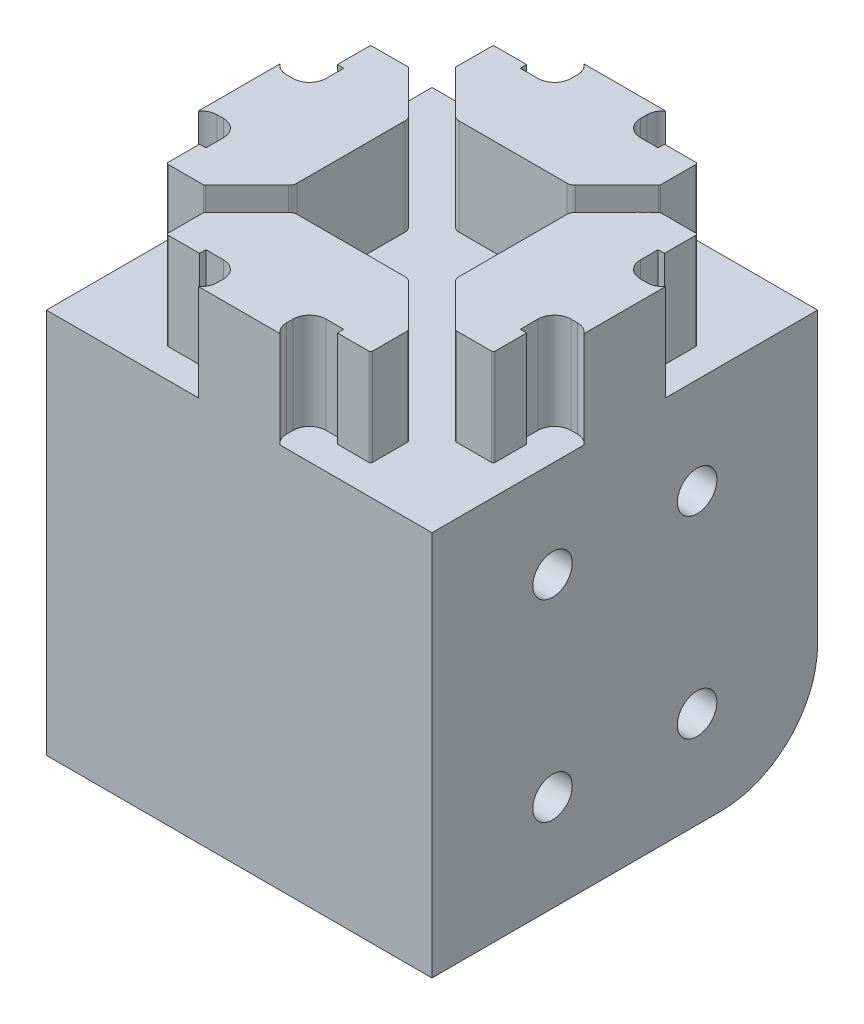
SolidWorks part; units mm, degrees
ref_plane "Front Plane" through (0, 0, 0) normal (0, 0, 1) x (1, 0, 0)
ref_plane "Top Plane" through (0, 0, 0) normal (0, 1, 0) x (1, 0, 0)
ref_plane "Right Plane" through (0, 0, 0) normal (1, 0, 0) x (0, 0, -1)
sketch "Sketch1" plane through (0, 0, 0) normal (0, 1, 0) x (1, 0, 0)
  line L1 (-20, -20) -> (20, -20)
  line L2 (-20, -20) -> (-20, 20)
  line L3 (-20, 20) -> (20, 20)
  line L4 (20, -20) -> (20, 20)
  line L5 (-20, -20) -> (20, 20) construction
  line L6 (-20, 20) -> (20, -20) construction
  point P0 (0, 0)
  dimension "D1" = 40
  dimension "D2" = 40
extrude "Boss-Extrude1" add sketch "Sketch1" along normal mid plane 40 contours L3 L4 L1 L2
sketch "Sketch2" plane through (0, 0, 0) normal (1, 0, 0) x (0, 0, -1)
  point P0 (0, 0)
  line B0 (-7.5, -10) -> (-7.5, 10) construction
  line B1 (7.5, -10) -> (7.5, 10) construction
  circle B2 centre (-7.5, 10) radius 2.05
  circle B3 centre (7.5, 10) radius 2.05
  circle B4 centre (-7.5, -10) radius 2.05
  circle B5 centre (7.5, -10) radius 2.05
sketch_block_instance "Block1-1"
sketch_block "Block1" parameters "D1"=4.1, "D2"=20, "D3"=15
extrude "Cut-Extrude1" cut sketch "Sketch2" against normal through all from offset 13
mirror "Mirror1" about plane through (0, 0, 0) normal (1, 0, 0) of "Cut-Extrude1"
sketch "Sketch3" plane through (0, 20, 0) normal (0, 1, 0) x (1, 0, 0)
  line L0 (11.8267, 9.3942) -> (11.8267, 9.4899)
  line L1 (11.8267, 9.4899) -> (11.9223, 9.4899)
  line L2 (11.9223, 9.4899) -> (12.39, 9.9576)
  line L3 (12.39, 9.9576) -> (12.39, 10.0532)
  line L4 (12.39, 10.0532) -> (12.4857, 10.0532)
  line L5 (12.4857, 10.0532) -> (12.9739, 10.5414)
  line L6 (13.1153, 10.6) -> (16.76, 10.6)
  line L7 (16.96, 10.4) -> (16.96, 7.15)
  line L8 (16.96, 7.15) -> (16.3, 7.15)
  line L9 (16.3, 7.15) -> (16.3, 5.32)
  line L10 (18.02, 3.6) -> (18.68, 3.6)
  line L11 (20.4, 5.32) -> (20.4, 17)
  line L12 (17, 20.4) -> (5.32, 20.4)
  line L13 (3.6, 18.68) -> (3.6, 18.02)
  line L14 (5.32, 16.3) -> (7.15, 16.3)
  line L15 (7.15, 16.3) -> (7.15, 16.96)
  line L16 (7.15, 16.96) -> (10.4, 16.96)
  line L17 (10.6, 16.76) -> (10.6, 13.1153)
  line L18 (10.5414, 12.9739) -> (6.237, 8.6695)
  line L19 (5.5865, 8.4) -> (-5.5865, 8.4)
  line L20 (-6.237, 8.6695) -> (-10.5414, 12.9739)
  line L21 (-10.6, 13.1153) -> (-10.6, 16.76)
  line L22 (-10.4, 16.96) -> (-7.15, 16.96)
  line L23 (-7.15, 16.96) -> (-7.15, 16.3)
  line L24 (-7.15, 16.3) -> (-5.32, 16.3)
  line L25 (-3.6, 18.02) -> (-3.6, 18.68)
  line L26 (-5.32, 20.4) -> (-17, 20.4)
  line L27 (-20.4, 17) -> (-20.4, 5.32)
  line L28 (-18.68, 3.6) -> (-18.02, 3.6)
  line L29 (-16.3, 5.32) -> (-16.3, 7.15)
  line L30 (-16.3, 7.15) -> (-16.96, 7.15)
  line L31 (-16.96, 7.15) -> (-16.96, 10.4)
  line L32 (-16.76, 10.6) -> (-13.1153, 10.6)
  line L33 (-12.9739, 10.5414) -> (-8.6695, 6.237)
  line L34 (-8.4, 5.5865) -> (-8.4, -5.5865)
  line L35 (-8.6695, -6.237) -> (-12.9739, -10.5414)
  line L36 (-13.1153, -10.6) -> (-16.76, -10.6)
  line L37 (-16.96, -10.4) -> (-16.96, -7.15)
  line L38 (-16.96, -7.15) -> (-16.3, -7.15)
  line L39 (-16.3, -7.15) -> (-16.3, -5.32)
  line L40 (-18.02, -3.6) -> (-18.68, -3.6)
  line L41 (-20.4, -5.32) -> (-20.4, -17)
  line L42 (-17, -20.4) -> (-5.32, -20.4)
  line L43 (-3.6, -18.68) -> (-3.6, -18.02)
  line L44 (-5.32, -16.3) -> (-7.15, -16.3)
  line L45 (-7.15, -16.3) -> (-7.15, -16.96)
  line L46 (-7.15, -16.96) -> (-10.4, -16.96)
  line L47 (-10.6, -16.76) -> (-10.6, -13.1153)
  line L48 (-10.5414, -12.9739) -> (-6.237, -8.6695)
  line L49 (-5.5865, -8.4) -> (5.5865, -8.4)
  line L50 (6.237, -8.6695) -> (10.5414, -12.9739)
  line L51 (10.6, -13.1153) -> (10.6, -16.76)
  line L52 (10.4, -16.96) -> (7.15, -16.96)
  line L53 (7.15, -16.96) -> (7.15, -16.3)
  line L54 (7.15, -16.3) -> (5.32, -16.3)
  line L55 (3.6, -18.02) -> (3.6, -18.68)
  line L56 (5.32, -20.4) -> (17, -20.4)
  line L57 (20.4, -17) -> (20.4, -5.32)
  line L58 (18.68, -3.6) -> (18.02, -3.6)
  line L59 (16.3, -5.32) -> (16.3, -7.15)
  line L60 (16.3, -7.15) -> (16.96, -7.15)
  line L61 (16.96, -7.15) -> (16.96, -10.4)
  line L62 (16.76, -10.6) -> (13.1153, -10.6)
  line L63 (12.9739, -10.5414) -> (8.6695, -6.237)
  line L64 (8.4, -5.5865) -> (8.4, 5.5865)
  line L65 (8.6695, 6.237) -> (11.8267, 9.3942)
  line L66 (11.4267, 9.5599) -> (11.4267, 9.8899)
  line L67 (11.4267, 9.8899) -> (11.7567, 9.8899)
  line L68 (11.7567, 9.8899) -> (11.99, 10.1232)
  line L69 (11.99, 10.1232) -> (11.99, 10.4532)
  line L70 (11.99, 10.4532) -> (12.32, 10.4532)
  line L71 (12.32, 10.4532) -> (12.691, 10.8243)
  line L72 (13.1153, 11) -> (16.76, 11)
  line L73 (17.36, 10.4) -> (17.36, 6.75)
  line L74 (17.36, 6.75) -> (16.7, 6.75)
  line L75 (16.7, 6.75) -> (16.7, 5.32)
  line L76 (18.02, 4) -> (18.68, 4)
  line L77 (20, 5.32) -> (20, 17)
  line L78 (17, 20) -> (5.32, 20)
  line L79 (4, 18.68) -> (4, 18.02)
  line L80 (5.32, 16.7) -> (6.75, 16.7)
  line L81 (6.75, 16.7) -> (6.75, 17.36)
  line L82 (6.75, 17.36) -> (10.4, 17.36)
  line L83 (11, 16.76) -> (11, 13.1153)
  line L84 (10.8243, 12.691) -> (6.5199, 8.3866)
  line L85 (5.5865, 8) -> (-5.5865, 8)
  line L86 (-6.5199, 8.3866) -> (-10.8243, 12.691)
  line L87 (-11, 13.1153) -> (-11, 16.76)
  line L88 (-10.4, 17.36) -> (-6.75, 17.36)
  line L89 (-6.75, 17.36) -> (-6.75, 16.7)
  line L90 (-6.75, 16.7) -> (-5.32, 16.7)
  line L91 (-4, 18.02) -> (-4, 18.68)
  line L92 (-5.32, 20) -> (-17, 20)
  line L93 (-20, 17) -> (-20, 5.32)
  line L94 (-18.68, 4) -> (-18.02, 4)
  line L95 (-16.7, 5.32) -> (-16.7, 6.75)
  line L96 (-16.7, 6.75) -> (-17.36, 6.75)
  line L97 (-17.36, 6.75) -> (-17.36, 10.4)
  line L98 (-16.76, 11) -> (-13.1153, 11)
  line L99 (-12.691, 10.8243) -> (-8.3866, 6.5199)
  line L100 (-8, 5.5865) -> (-8, -5.5865)
  line L101 (-8.3866, -6.5199) -> (-12.691, -10.8243)
  line L102 (-13.1153, -11) -> (-16.76, -11)
  line L103 (-17.36, -10.4) -> (-17.36, -6.75)
  line L104 (-17.36, -6.75) -> (-16.7, -6.75)
  line L105 (-16.7, -6.75) -> (-16.7, -5.32)
  line L106 (-18.02, -4) -> (-18.68, -4)
  line L107 (-20, -5.32) -> (-20, -17)
  line L108 (-17, -20) -> (-5.32, -20)
  line L109 (-4, -18.68) -> (-4, -18.02)
  line L110 (-5.32, -16.7) -> (-6.75, -16.7)
  line L111 (-6.75, -16.7) -> (-6.75, -17.36)
  line L112 (-6.75, -17.36) -> (-10.4, -17.36)
  line L113 (-11, -16.76) -> (-11, -13.1153)
  line L114 (-10.8243, -12.691) -> (-6.5199, -8.3866)
  line L115 (-5.5865, -8) -> (5.5865, -8)
  line L116 (6.5199, -8.3866) -> (10.8243, -12.691)
  line L117 (11, -13.1153) -> (11, -16.76)
  line L118 (10.4, -17.36) -> (6.75, -17.36)
  line L119 (6.75, -17.36) -> (6.75, -16.7)
  line L120 (6.75, -16.7) -> (5.32, -16.7)
  line L121 (4, -18.02) -> (4, -18.68)
  line L122 (5.32, -20) -> (17, -20)
  line L123 (20, -17) -> (20, -5.32)
  line L124 (18.68, -4) -> (18.02, -4)
  line L125 (16.7, -5.32) -> (16.7, -6.75)
  line L126 (16.7, -6.75) -> (17.36, -6.75)
  line L127 (17.36, -6.75) -> (17.36, -10.4)
  line L128 (16.76, -11) -> (13.1153, -11)
  line L129 (12.691, -10.8243) -> (8.3866, -6.5199)
  line L130 (8, -5.5865) -> (8, 5.5865)
  line L131 (8.3866, 6.5199) -> (11.4267, 9.5599)
  line L132 (11.4267, 9.5599) -> (11.4267, 9.8899)
  line L133 (11.4267, 9.8899) -> (11.7567, 9.8899)
  line L134 (11.7567, 9.8899) -> (11.99, 10.1232)
  line L135 (11.99, 10.1232) -> (11.99, 10.4532)
  line L136 (11.99, 10.4532) -> (12.32, 10.4532)
  line L137 (12.32, 10.4532) -> (12.691, 10.8243)
  line L138 (13.1153, 11) -> (16.76, 11)
  line L139 (17.36, 10.4) -> (17.36, 6.75)
  line L140 (17.36, 6.75) -> (16.7, 6.75)
  line L141 (16.7, 6.75) -> (16.7, 5.32)
  line L142 (18.02, 4) -> (18.68, 4)
  line L143 (20, 5.32) -> (20, 17)
  line L144 (17, 20) -> (5.32, 20)
  line L145 (4, 18.68) -> (4, 18.02)
  line L146 (5.32, 16.7) -> (6.75, 16.7)
  line L147 (6.75, 16.7) -> (6.75, 17.36)
  line L148 (6.75, 17.36) -> (10.4, 17.36)
  line L149 (11, 16.76) -> (11, 13.1153)
  line L150 (10.8243, 12.691) -> (6.5199, 8.3866)
  line L151 (5.5865, 8) -> (-5.5865, 8)
  line L152 (-6.5199, 8.3866) -> (-10.8243, 12.691)
  line L153 (-11, 13.1153) -> (-11, 16.76)
  line L154 (-10.4, 17.36) -> (-6.75, 17.36)
  line L155 (-6.75, 17.36) -> (-6.75, 16.7)
  line L156 (-6.75, 16.7) -> (-5.32, 16.7)
  line L157 (-4, 18.02) -> (-4, 18.68)
  line L158 (-5.32, 20) -> (-17, 20)
  line L159 (-20, 17) -> (-20, 5.32)
  line L160 (-18.68, 4) -> (-18.02, 4)
  line L161 (-16.7, 5.32) -> (-16.7, 6.75)
  line L162 (-16.7, 6.75) -> (-17.36, 6.75)
  line L163 (-17.36, 6.75) -> (-17.36, 10.4)
  line L164 (-16.76, 11) -> (-13.1153, 11)
  line L165 (-12.691, 10.8243) -> (-8.3866, 6.5199)
  line L166 (-8, 5.5865) -> (-8, -5.5865)
  line L167 (-8.3866, -6.5199) -> (-12.691, -10.8243)
  line L168 (-13.1153, -11) -> (-16.76, -11)
  line L169 (-17.36, -10.4) -> (-17.36, -6.75)
  line L170 (-17.36, -6.75) -> (-16.7, -6.75)
  line L171 (-16.7, -6.75) -> (-16.7, -5.32)
  line L172 (-18.02, -4) -> (-18.68, -4)
  line L173 (-20, -5.32) -> (-20, -17)
  line L174 (-17, -20) -> (-5.32, -20)
  line L175 (-4, -18.68) -> (-4, -18.02)
  line L176 (-5.32, -16.7) -> (-6.75, -16.7)
  line L177 (-6.75, -16.7) -> (-6.75, -17.36)
  line L178 (-6.75, -17.36) -> (-10.4, -17.36)
  line L179 (-11, -16.76) -> (-11, -13.1153)
  line L180 (-10.8243, -12.691) -> (-6.5199, -8.3866)
  line L181 (-5.5865, -8) -> (5.5865, -8)
  line L182 (6.5199, -8.3866) -> (10.8243, -12.691)
  line L183 (11, -13.1153) -> (11, -16.76)
  line L184 (10.4, -17.36) -> (6.75, -17.36)
  line L185 (6.75, -17.36) -> (6.75, -16.7)
  line L186 (6.75, -16.7) -> (5.32, -16.7)
  line L187 (4, -18.02) -> (4, -18.68)
  line L188 (5.32, -20) -> (17, -20)
  line L189 (20, -17) -> (20, -5.32)
  line L190 (18.68, -4) -> (18.02, -4)
  line L191 (16.7, -5.32) -> (16.7, -6.75)
  line L192 (16.7, -6.75) -> (17.36, -6.75)
  line L193 (17.36, -6.75) -> (17.36, -10.4)
  line L194 (16.76, -11) -> (13.1153, -11)
  line L195 (12.691, -10.8243) -> (8.3866, -6.5199)
  line L196 (8, -5.5865) -> (8, 5.5865)
  line L197 (8.3866, 6.5199) -> (11.4267, 9.5599)
  line L202 (-20, 20) -> (-20, -20)
  line L203 (-20, -20) -> (20, -20)
  line L204 (20, -20) -> (20, 20)
  line L205 (20, 20) -> (-20, 20)
  line L206 (-20, 20) -> (-20, -20)
  line L207 (-20, -20) -> (20, -20)
  line L208 (20, -20) -> (20, 20)
  line L209 (20, 20) -> (-20, 20)
  arc A0 (13.1153, 10.6) -> (12.9739, 10.5414) centre (13.1153, 10.4) ccw
  arc A1 (16.96, 10.4) -> (16.76, 10.6) centre (16.76, 10.4) ccw
  arc A2 (16.3, 5.32) -> (18.02, 3.6) centre (18.02, 5.32) ccw
  arc A3 (18.68, 3.6) -> (20.4, 5.32) centre (18.68, 5.32) ccw
  arc A4 (20.4, 17) -> (17, 20.4) centre (17, 17) ccw
  arc A5 (5.32, 20.4) -> (3.6, 18.68) centre (5.32, 18.68) ccw
  arc A6 (3.6, 18.02) -> (5.32, 16.3) centre (5.32, 18.02) ccw
  arc A7 (10.6, 16.76) -> (10.4, 16.96) centre (10.4, 16.76) ccw
  arc A8 (10.5414, 12.9739) -> (10.6, 13.1153) centre (10.4, 13.1153) ccw
  arc A9 (5.5865, 8.4) -> (6.237, 8.6695) centre (5.5865, 9.32) ccw
  arc A10 (-6.237, 8.6695) -> (-5.5865, 8.4) centre (-5.5865, 9.32) ccw
  arc A11 (-10.6, 13.1153) -> (-10.5414, 12.9739) centre (-10.4, 13.1153) ccw
  arc A12 (-10.4, 16.96) -> (-10.6, 16.76) centre (-10.4, 16.76) ccw
  arc A13 (-5.32, 16.3) -> (-3.6, 18.02) centre (-5.32, 18.02) ccw
  arc A14 (-3.6, 18.68) -> (-5.32, 20.4) centre (-5.32, 18.68) ccw
  arc A15 (-17, 20.4) -> (-20.4, 17) centre (-17, 17) ccw
  arc A16 (-20.4, 5.32) -> (-18.68, 3.6) centre (-18.68, 5.32) ccw
  arc A17 (-18.02, 3.6) -> (-16.3, 5.32) centre (-18.02, 5.32) ccw
  arc A18 (-16.76, 10.6) -> (-16.96, 10.4) centre (-16.76, 10.4) ccw
  arc A19 (-12.9739, 10.5414) -> (-13.1153, 10.6) centre (-13.1153, 10.4) ccw
  arc A20 (-8.4, 5.5865) -> (-8.6695, 6.237) centre (-9.32, 5.5865) ccw
  arc A21 (-8.6695, -6.237) -> (-8.4, -5.5865) centre (-9.32, -5.5865) ccw
  arc A22 (-13.1153, -10.6) -> (-12.9739, -10.5414) centre (-13.1153, -10.4) ccw
  arc A23 (-16.96, -10.4) -> (-16.76, -10.6) centre (-16.76, -10.4) ccw
  arc A24 (-16.3, -5.32) -> (-18.02, -3.6) centre (-18.02, -5.32) ccw
  arc A25 (-18.68, -3.6) -> (-20.4, -5.32) centre (-18.68, -5.32) ccw
  arc A26 (-20.4, -17) -> (-17, -20.4) centre (-17, -17) ccw
  arc A27 (-5.32, -20.4) -> (-3.6, -18.68) centre (-5.32, -18.68) ccw
  arc A28 (-3.6, -18.02) -> (-5.32, -16.3) centre (-5.32, -18.02) ccw
  arc A29 (-10.6, -16.76) -> (-10.4, -16.96) centre (-10.4, -16.76) ccw
  arc A30 (-10.5414, -12.9739) -> (-10.6, -13.1153) centre (-10.4, -13.1153) ccw
  arc A31 (-5.5865, -8.4) -> (-6.237, -8.6695) centre (-5.5865, -9.32) ccw
  arc A32 (6.237, -8.6695) -> (5.5865, -8.4) centre (5.5865, -9.32) ccw
  arc A33 (10.6, -13.1153) -> (10.5414, -12.9739) centre (10.4, -13.1153) ccw
  arc A34 (10.4, -16.96) -> (10.6, -16.76) centre (10.4, -16.76) ccw
  arc A35 (5.32, -16.3) -> (3.6, -18.02) centre (5.32, -18.02) ccw
  arc A36 (3.6, -18.68) -> (5.32, -20.4) centre (5.32, -18.68) ccw
  arc A37 (17, -20.4) -> (20.4, -17) centre (17, -17) ccw
  arc A38 (20.4, -5.32) -> (18.68, -3.6) centre (18.68, -5.32) ccw
  arc A39 (18.02, -3.6) -> (16.3, -5.32) centre (18.02, -5.32) ccw
  arc A40 (16.76, -10.6) -> (16.96, -10.4) centre (16.76, -10.4) ccw
  arc A41 (12.9739, -10.5414) -> (13.1153, -10.6) centre (13.1153, -10.4) ccw
  arc A42 (8.4, -5.5865) -> (8.6695, -6.237) centre (9.32, -5.5865) ccw
  arc A43 (8.6695, 6.237) -> (8.4, 5.5865) centre (9.32, 5.5865) ccw
  arc A44 (13.1153, 11) -> (12.691, 10.8243) centre (13.1153, 10.4) ccw
  arc A45 (17.36, 10.4) -> (16.76, 11) centre (16.76, 10.4) ccw
  arc A46 (16.7, 5.32) -> (18.02, 4) centre (18.02, 5.32) ccw
  arc A47 (18.68, 4) -> (20, 5.32) centre (18.68, 5.32) ccw
  arc A48 (20, 17) -> (17, 20) centre (17, 17) ccw
  arc A49 (5.32, 20) -> (4, 18.68) centre (5.32, 18.68) ccw
  arc A50 (4, 18.02) -> (5.32, 16.7) centre (5.32, 18.02) ccw
  arc A51 (11, 16.76) -> (10.4, 17.36) centre (10.4, 16.76) ccw
  arc A52 (10.8243, 12.691) -> (11, 13.1153) centre (10.4, 13.1153) ccw
  arc A53 (5.5865, 8) -> (6.5199, 8.3866) centre (5.5865, 9.32) ccw
  arc A54 (-6.5199, 8.3866) -> (-5.5865, 8) centre (-5.5865, 9.32) ccw
  arc A55 (-11, 13.1153) -> (-10.8243, 12.691) centre (-10.4, 13.1153) ccw
  arc A56 (-10.4, 17.36) -> (-11, 16.76) centre (-10.4, 16.76) ccw
  arc A57 (-5.32, 16.7) -> (-4, 18.02) centre (-5.32, 18.02) ccw
  arc A58 (-4, 18.68) -> (-5.32, 20) centre (-5.32, 18.68) ccw
  arc A59 (-17, 20) -> (-20, 17) centre (-17, 17) ccw
  arc A60 (-20, 5.32) -> (-18.68, 4) centre (-18.68, 5.32) ccw
  arc A61 (-18.02, 4) -> (-16.7, 5.32) centre (-18.02, 5.32) ccw
  arc A62 (-16.76, 11) -> (-17.36, 10.4) centre (-16.76, 10.4) ccw
  arc A63 (-12.691, 10.8243) -> (-13.1153, 11) centre (-13.1153, 10.4) ccw
  arc A64 (-8, 5.5865) -> (-8.3866, 6.5199) centre (-9.32, 5.5865) ccw
  arc A65 (-8.3866, -6.5199) -> (-8, -5.5865) centre (-9.32, -5.5865) ccw
  arc A66 (-13.1153, -11) -> (-12.691, -10.8243) centre (-13.1153, -10.4) ccw
  arc A67 (-17.36, -10.4) -> (-16.76, -11) centre (-16.76, -10.4) ccw
  arc A68 (-16.7, -5.32) -> (-18.02, -4) centre (-18.02, -5.32) ccw
  arc A69 (-18.68, -4) -> (-20, -5.32) centre (-18.68, -5.32) ccw
  arc A70 (-20, -17) -> (-17, -20) centre (-17, -17) ccw
  arc A71 (-5.32, -20) -> (-4, -18.68) centre (-5.32, -18.68) ccw
  arc A72 (-4, -18.02) -> (-5.32, -16.7) centre (-5.32, -18.02) ccw
  arc A73 (-11, -16.76) -> (-10.4, -17.36) centre (-10.4, -16.76) ccw
  arc A74 (-10.8243, -12.691) -> (-11, -13.1153) centre (-10.4, -13.1153) ccw
  arc A75 (-5.5865, -8) -> (-6.5199, -8.3866) centre (-5.5865, -9.32) ccw
  arc A76 (6.5199, -8.3866) -> (5.5865, -8) centre (5.5865, -9.32) ccw
  arc A77 (11, -13.1153) -> (10.8243, -12.691) centre (10.4, -13.1153) ccw
  arc A78 (10.4, -17.36) -> (11, -16.76) centre (10.4, -16.76) ccw
  arc A79 (5.32, -16.7) -> (4, -18.02) centre (5.32, -18.02) ccw
  arc A80 (4, -18.68) -> (5.32, -20) centre (5.32, -18.68) ccw
  arc A81 (17, -20) -> (20, -17) centre (17, -17) ccw
  arc A82 (20, -5.32) -> (18.68, -4) centre (18.68, -5.32) ccw
  arc A83 (18.02, -4) -> (16.7, -5.32) centre (18.02, -5.32) ccw
  arc A84 (16.76, -11) -> (17.36, -10.4) centre (16.76, -10.4) ccw
  arc A85 (12.691, -10.8243) -> (13.1153, -11) centre (13.1153, -10.4) ccw
  arc A86 (8, -5.5865) -> (8.3866, -6.5199) centre (9.32, -5.5865) ccw
  arc A87 (8.3866, 6.5199) -> (8, 5.5865) centre (9.32, 5.5865) ccw
  arc A88 (13.1153, 11) -> (12.691, 10.8243) centre (13.1153, 10.4) ccw
  arc A89 (17.36, 10.4) -> (16.76, 11) centre (16.76, 10.4) ccw
  arc A90 (16.7, 5.32) -> (18.02, 4) centre (18.02, 5.32) ccw
  arc A91 (18.68, 4) -> (20, 5.32) centre (18.68, 5.32) ccw
  arc A92 (20, 17) -> (17, 20) centre (17, 17) ccw
  arc A93 (5.32, 20) -> (4, 18.68) centre (5.32, 18.68) ccw
  arc A94 (4, 18.02) -> (5.32, 16.7) centre (5.32, 18.02) ccw
  arc A95 (11, 16.76) -> (10.4, 17.36) centre (10.4, 16.76) ccw
  arc A96 (10.8243, 12.691) -> (11, 13.1153) centre (10.4, 13.1153) ccw
  arc A97 (5.5865, 8) -> (6.5199, 8.3866) centre (5.5865, 9.32) ccw
  arc A98 (-6.5199, 8.3866) -> (-5.5865, 8) centre (-5.5865, 9.32) ccw
  arc A99 (-11, 13.1153) -> (-10.8243, 12.691) centre (-10.4, 13.1153) ccw
  arc A100 (-10.4, 17.36) -> (-11, 16.76) centre (-10.4, 16.76) ccw
  arc A101 (-5.32, 16.7) -> (-4, 18.02) centre (-5.32, 18.02) ccw
  arc A102 (-4, 18.68) -> (-5.32, 20) centre (-5.32, 18.68) ccw
  arc A103 (-17, 20) -> (-20, 17) centre (-17, 17) ccw
  arc A104 (-20, 5.32) -> (-18.68, 4) centre (-18.68, 5.32) ccw
  arc A105 (-18.02, 4) -> (-16.7, 5.32) centre (-18.02, 5.32) ccw
  arc A106 (-16.76, 11) -> (-17.36, 10.4) centre (-16.76, 10.4) ccw
  arc A107 (-12.691, 10.8243) -> (-13.1153, 11) centre (-13.1153, 10.4) ccw
  arc A108 (-8, 5.5865) -> (-8.3866, 6.5199) centre (-9.32, 5.5865) ccw
  arc A109 (-8.3866, -6.5199) -> (-8, -5.5865) centre (-9.32, -5.5865) ccw
  arc A110 (-13.1153, -11) -> (-12.691, -10.8243) centre (-13.1153, -10.4) ccw
  arc A111 (-17.36, -10.4) -> (-16.76, -11) centre (-16.76, -10.4) ccw
  arc A112 (-16.7, -5.32) -> (-18.02, -4) centre (-18.02, -5.32) ccw
  arc A113 (-18.68, -4) -> (-20, -5.32) centre (-18.68, -5.32) ccw
  arc A114 (-20, -17) -> (-17, -20) centre (-17, -17) ccw
  arc A115 (-5.32, -20) -> (-4, -18.68) centre (-5.32, -18.68) ccw
  arc A116 (-4, -18.02) -> (-5.32, -16.7) centre (-5.32, -18.02) ccw
  arc A117 (-11, -16.76) -> (-10.4, -17.36) centre (-10.4, -16.76) ccw
  arc A118 (-10.8243, -12.691) -> (-11, -13.1153) centre (-10.4, -13.1153) ccw
  arc A119 (-5.5865, -8) -> (-6.5199, -8.3866) centre (-5.5865, -9.32) ccw
  arc A120 (6.5199, -8.3866) -> (5.5865, -8) centre (5.5865, -9.32) ccw
  arc A121 (11, -13.1153) -> (10.8243, -12.691) centre (10.4, -13.1153) ccw
  arc A122 (10.4, -17.36) -> (11, -16.76) centre (10.4, -16.76) ccw
  arc A123 (5.32, -16.7) -> (4, -18.02) centre (5.32, -18.02) ccw
  arc A124 (4, -18.68) -> (5.32, -20) centre (5.32, -18.68) ccw
  arc A125 (17, -20) -> (20, -17) centre (17, -17) ccw
  arc A126 (20, -5.32) -> (18.68, -4) centre (18.68, -5.32) ccw
  arc A127 (18.02, -4) -> (16.7, -5.32) centre (18.02, -5.32) ccw
  arc A128 (16.76, -11) -> (17.36, -10.4) centre (16.76, -10.4) ccw
  arc A129 (12.691, -10.8243) -> (13.1153, -11) centre (13.1153, -10.4) ccw
  arc A130 (8, -5.5865) -> (8.3866, -6.5199) centre (9.32, -5.5865) ccw
  arc A131 (8.3866, 6.5199) -> (8, 5.5865) centre (9.32, 5.5865) ccw
  dimension "D1" = 0
  dimension "D2" = 0.4
  dimension "D3" = 0
extrude "Boss-Extrude2" add sketch "Sketch3" along normal blind 10 contours A25 L40 A24 L39 L38 L37 A23 L36 A22 L35 A21 L34 A20 L33 A19 L32 A18 L31 L30 L29 A17 L28 A16 L206 | A14 L25 A13 L24 L23 L22 A12 L21 A11 L20 A10 L19 A9 L18 A8 L17 A7 L16 L15 L14 A6 L13 A5 L209 | L65 A43 L64 A42 L63 A41 L62 A40 L61 L60 L59 A39 L58 A38 L208 A3 L10 A2 L9 L8 L7 A1 L6 A0 L5 L4 L3 L2 L1 L0 | A36 L55 A35 L54 L53 L52 A34 L51 A33 L50 A32 L49 A31 L48 A30 L47 A29 L46 L45 L44 A28 L43 A27 L207 region at (13.6624, 20, -0.0005) region at (0, 20, 13.6625) region at (0, 20, -13.6625) region at (-13.6625, 20, 0)
fillet "Fillet1" radius 10 1 edges at (0, -20, -20)
